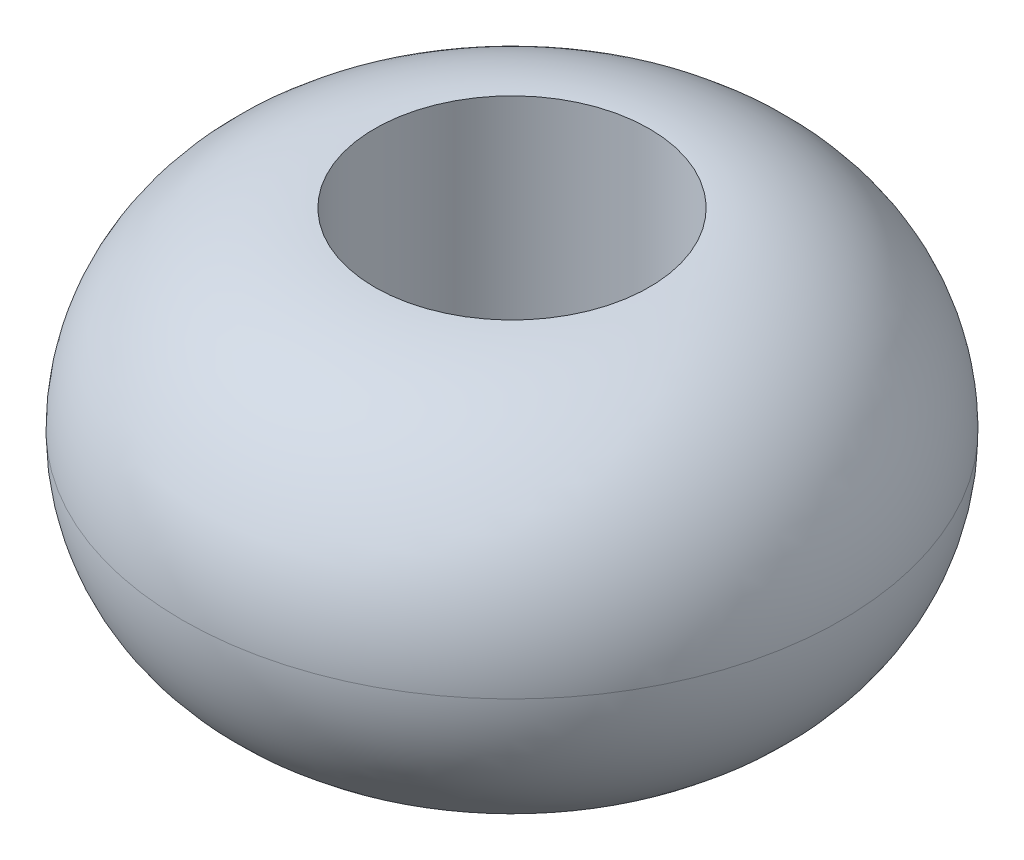
SolidWorks part; units mm, degrees
ref_plane "Płaszczyzna przednia" through (0, 0, 0) normal (0, 0, 1) x (1, 0, 0)
ref_plane "Płaszczyzna górna" through (0, 0, 0) normal (0, 1, 0) x (1, 0, 0)
ref_plane "Płaszczyzna prawa" through (0, 0, 0) normal (1, 0, 0) x (0, 0, -1)
sketch "Szkic1" plane through (0, 0, 0) normal (0, 1, 0) x (1, 0, 0)
  circle A0 centre (0, 0) radius 60
extrude "Dodanie-wyciągnięcie1" add sketch "Szkic1" along normal blind 70
sketch "Szkic2" plane through (0, 70, 0) normal (0, 1, 0) x (1, 0, 0)
  circle A0 centre (0, 0) radius 25
extrude "Wytnij-wyciągnięcie1" cut sketch "Szkic2" against normal blind 70
fillet "Zaokrąglenie2" radius 35 2 edges at (0, 0, 60) (0, 70, 60)
